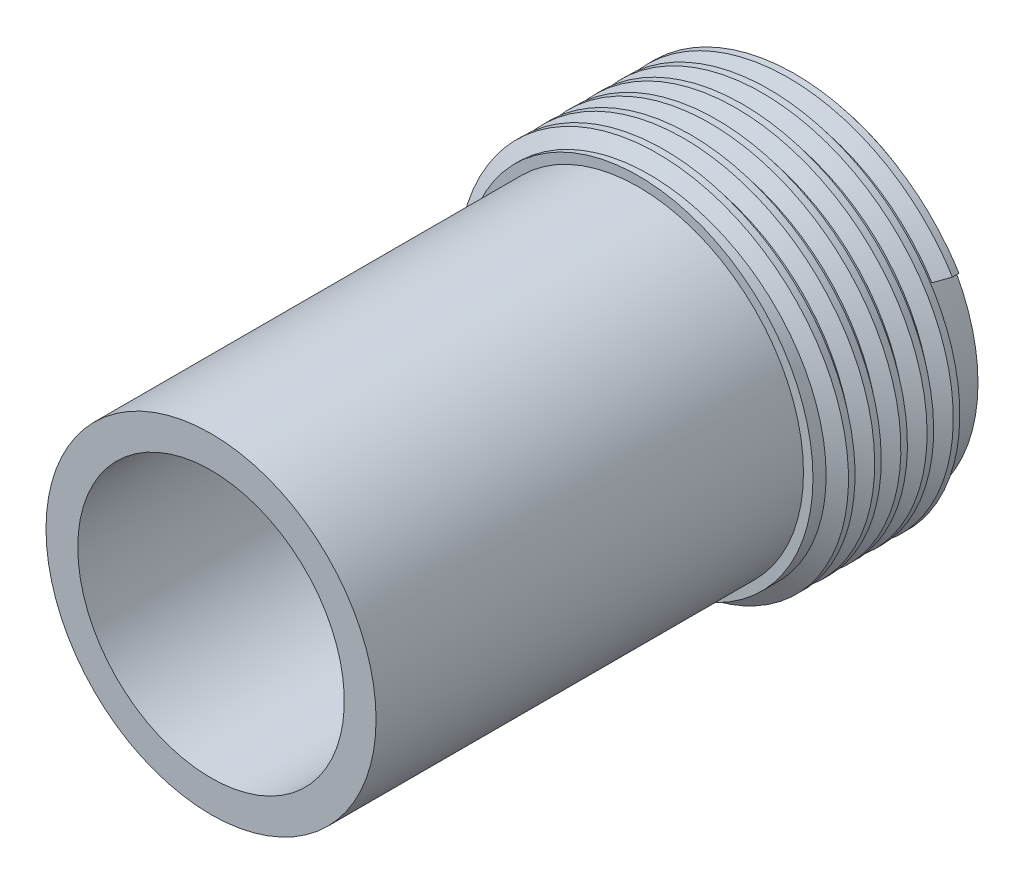
SolidWorks part; units mm, degrees
ref_plane "Plano frontal" through (0, 0, 0) normal (0, 0, 1) x (1, 0, 0)
ref_plane "Plano superior" through (0, 0, 0) normal (0, 1, 0) x (1, 0, 0)
ref_plane "Plano direito" through (0, 0, 0) normal (1, 0, 0) x (0, 0, -1)
ref_plane "Plano1" through (0, 0, 0) normal (0, -1, 0) x (1, 0, 0)
sketch "Esboço1" plane through (0, 0, 0) normal (0, -1, 0) x (1, 0, 0)
  line L0 (14.6396, -2.7347) -> (18.6396, -2.7347)
  line L1 (18.6396, -2.7347) -> (18.6396, 17.2653)
  line L2 (18.6396, 17.2653) -> (17.4896, 17.2653)
  line L3 (17.4896, 17.2653) -> (17.4896, 69.0612)
  line L4 (17.4896, 69.0612) -> (13.6396, 69.0612)
  line L5 (13.6396, 69.0612) -> (13.6396, 17.2653)
  line L6 (13.6396, 17.2653) -> (14.6396, 17.2653)
  line L7 (14.6396, 17.2653) -> (14.6396, -2.7347)
  line L8 (-2.5104, 69.0612) -> (-2.5104, 0) construction
  dimension "D1" = 21.15
  dimension "D2" = 20
  dimension "D3" = 16.15
  dimension "D4" = 1
  dimension "D5" = 20
revolve "Revolução1" add sketch "Esboço1" angle 360 about L8 reverse direction yes
thread "Rosca1" pitch 3.175 method extrude profile "Perfil da rosca1" start angle 0, offset 0, length 17.2, pitch 3.175, diameter 42.3
ref_plane "Plano2" through (-23.6604, 0, 17.2653) normal (0, 1, 0) x (1, 0, 0)
sketch "Perfil da rosca1" plane through (-23.6604, 0, 17.2653) normal (0, 1, 0) x (1, 0, 0)
  line L0 (0, 0) -> (0, 3.175) construction
  line L11 (0, 0) -> (0, 2.7781)
  line L12 (0, 2.7781) -> (-1.7185, 1.7859)
  line L13 (-1.7185, 1.7859) -> (-1.7185, 0.9922)
  line L15 (-1.7185, 0.9922) -> (0, 0)
  line L17 (-1.7185, 1.3891) -> (0, 1.3891) construction
  point P2 (0, 0)
  dimension "Pitch" = 3.175
  dimension "Profile_Angle" = 60
  dimension "Profile_Land" = 0.7937
  dimension "Profile_Height" = 1.7185
